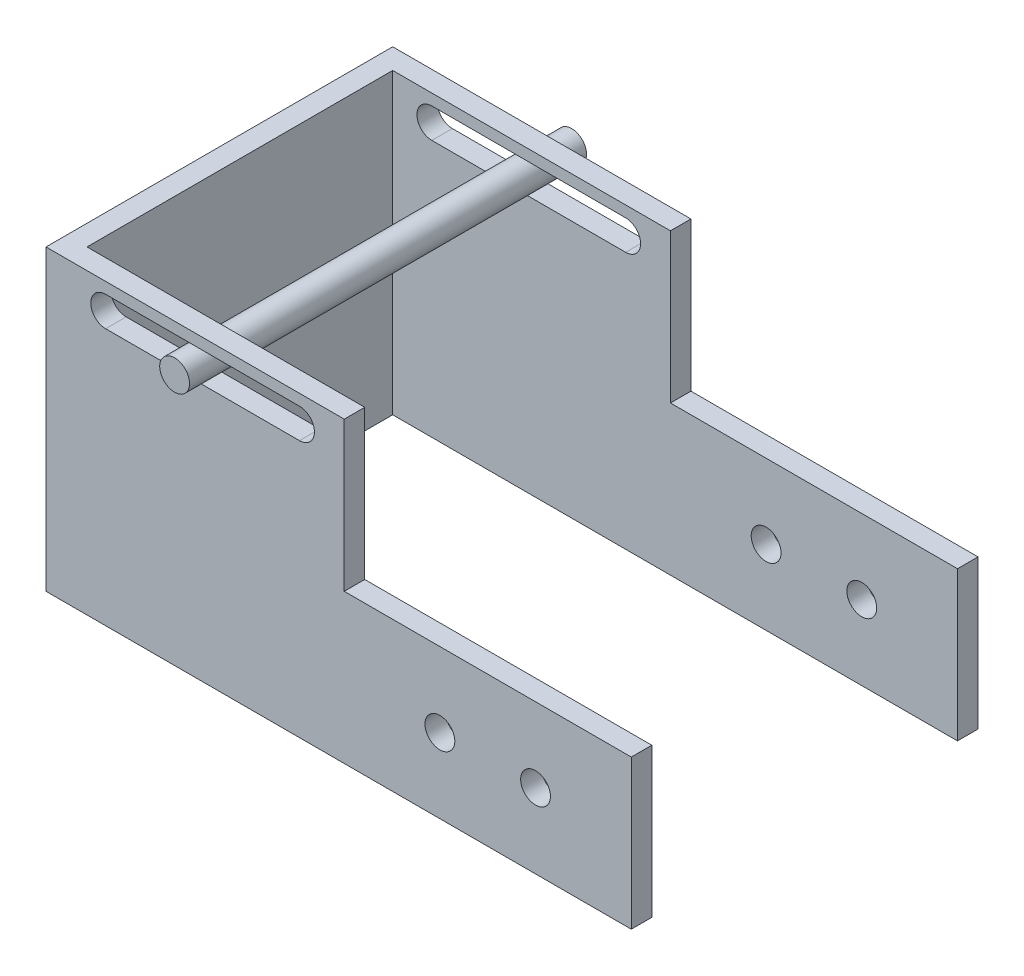
SolidWorks part; units mm, degrees
ref_plane "Front Plane" through (0, 0, 0) normal (0, 0, 1) x (1, 0, 0)
ref_plane "Top Plane" through (0, 0, 0) normal (0, 1, 0) x (1, 0, 0)
ref_plane "Right Plane" through (0, 0, 0) normal (1, 0, 0) x (0, 0, -1)
sketch "Sketch1" plane through (0, 0, 0) normal (0, 0, 1) x (1, 0, 0)
  line L0 (0, 0) -> (38.5, 0)
  line L1 (-40, -20) -> (38.5, -20)
  line L2 (-40, -20) -> (-40, 20)
  line L3 (-40, 20) -> (0, 20)
  line L4 (38.5, -20) -> (38.5, 0)
  line L5 (0, 20) -> (0, -20) construction
  line L6 (-40, 0) -> (38.5, 0) construction
  line L7 (0, 0) -> (0, 20)
  line L8 (-32, 18.5) -> (-6, 18.5)
  line L9 (-32, 14.5) -> (-6, 14.5)
  circle A0 centre (12.83, -10) radius 2
  circle A1 centre (25.66, -10) radius 2
  circle A2 centre (-20, 16.5) radius 2
  arc A3 (-6, 18.5) -> (-6, 14.5) centre (-6, 16.5) cw
  arc A4 (-32, 18.5) -> (-32, 14.5) centre (-32, 16.5) ccw
  point P0 (0, 0)
  point P9 (38.5, -10)
  point P19 (-4, 16.5)
  dimension "D4" = 4
  dimension "D7" = 1.5
  dimension "D8" = 4
  dimension "D11" = 8
  dimension "D1" = 78.5
  dimension "D2" = 40
  dimension "D3" = 38.5
  dimension "D5" = 12.83
  dimension "D6" = 12.83
  dimension "D9" = 20
  dimension "D10" = 4
extrude "Boss-Extrude1" add sketch "Sketch1" along normal blind 2.75 contours L0 L7 L3 L2 L1 L4 A4 L8 A3 L9 A1 A0 region at (-6.9319, -4.2059, 0)
extrude "Boss-Extrude2" add sketch "Sketch1<4>" along normal blind 53.25 from offset 4 separate body contours A2 offset against normal yes
sketch "Sketch1<4>" plane through (0, 0, 0) normal (0, 0, 1) x (1, 0, 0) same geometry as "Sketch1"
sketch "Sketch2" plane through (0, 0, 2.75) normal (0, 0, 1) x (1, 0, 0)
  line L0 (-40, -20) -> (38.5, -20) construction
  line L1 (-40, 20) -> (-37.25, 20)
  line L2 (-40, 20) -> (-40, -20)
  line L3 (-40, -20) -> (-37.25, -20)
  line L4 (-37.25, 20) -> (-37.25, -20)
  dimension "D1" = 2.75
extrude "Boss-Extrude3" add sketch "Sketch2" along normal blind 43.75
pattern_linear "LPattern1" count 2 spacing 43.75 along (0, 0, 1) of "Boss-Extrude1"
